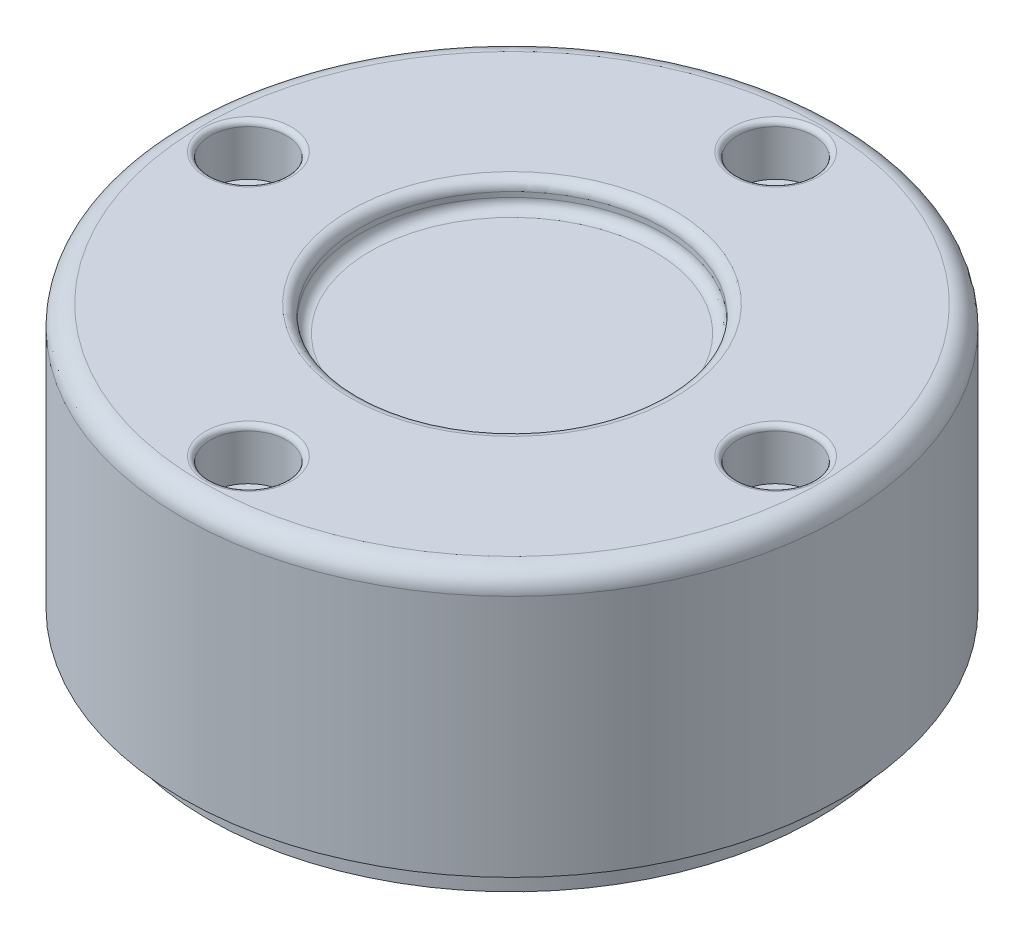
SolidWorks part; units mm, degrees
material "2014-O"
ref_plane "Front Plane" through (0, 0, 0) normal (0, 0, 1) x (1, 0, 0)
ref_plane "Top Plane" through (0, 0, 0) normal (0, 1, 0) x (1, 0, 0)
ref_plane "Right Plane" through (0, 0, 0) normal (1, 0, 0) x (0, 0, -1)
sketch "Sketch2" plane through (0, 0, 0) normal (0, 1, 0) x (1, 0, 0)
  circle A0 centre (0, 0) radius 30
  dimension "D1" = 60
extrude "Boss-Extrude1" add sketch "Sketch2" along normal blind 3
sketch "Sketch3" plane through (0, 3, 0) normal (0, 1, 0) x (1, 0, 0)
  circle A0 centre (0, 0) radius 32.5
  dimension "D1" = 65
extrude "Boss-Extrude2" add sketch "Sketch3" along normal blind 26
sketch "Sketch4" plane through (0, 29, 0) normal (0, 1, 0) x (1, 0, 0)
  line L0 (0, 0) -> (0, 26) construction
  circle A0 centre (0, 0) radius 15
  circle A2 centre (0, 0) radius 32.5 construction
  circle A3 centre (0, 26) radius 3.75
  circle A4 centre (26, 0) radius 3.75
  circle A5 centre (0, -26) radius 3.75
  circle A6 centre (-26, 0) radius 3.75
  point P17 (0, 0)
  dimension "D1" = 30
  dimension "D2" = 26
  dimension "D3" = 7.5
  dimension "D4" = 4
extrude "Cut-Extrude1" cut sketch "Sketch4" against normal blind 2.5 contours A0
extrude "Cut-Extrude2" cut sketch "Sketch4<3>" against normal blind 5 contours A6 | A3 | A4 | A5 region at (0, 29, -26) region at (26, 29, 0) region at (-26, 29, 0)
sketch "Sketch4<3>" plane through (0, 29, 0) normal (0, 1, 0) x (1, 0, 0) same geometry as "Sketch4"
fillet "Fillet1" radius 1 1 edges at (0, 26.5, 15)
fillet "Fillet2" radius 1 1 edges at (0, 29, 15)
fillet "Fillet3" radius 2 1 edges at (0, 29, 32.5)
fillet "Fillet4" radius 0.5 4 edges at (0, 29, 29.75) (26, 29, 3.75) (0, 29, -22.25) (-26, 29, 3.75)
shell "Shell1" thickness 2.5 removed face at (0, 0, 30)
